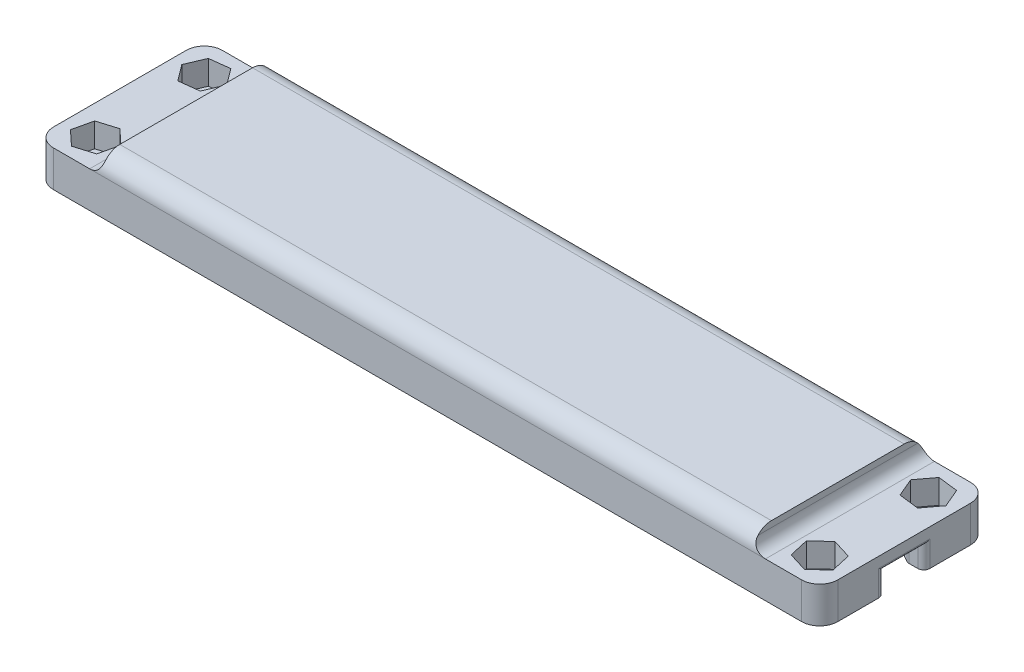
SolidWorks part; units mm, degrees
ref_plane "Front Plane" through (0, 0, 0) normal (0, 0, 1) x (1, 0, 0)
ref_plane "Top Plane" through (0, 0, 0) normal (0, 1, 0) x (1, 0, 0)
ref_plane "Right Plane" through (0, 0, 0) normal (1, 0, 0) x (0, 0, -1)
sketch "Sketch1" plane through (0, 0, 0) normal (0, 1, 0) x (1, 0, 0)
  line L1 (65, -14) -> (-65, -14)
  line L2 (65, -14) -> (65, 14)
  line L3 (65, 14) -> (-65, 14)
  line L4 (-65, -14) -> (-65, 14)
  line L5 (65, -14) -> (-65, 14) construction
  line L6 (65, 14) -> (-65, -14) construction
  point P0 (0, 0)
  dimension "D1" = 28
  dimension "D2" = 130
extrude "Boss-Extrude1" add sketch "Sketch1" along normal blind 9
sketch "Sketch2" plane through (0, 0, 0) normal (0, 1, 0) x (1, 0, 0)
  line L0 (-51, 7.5) -> (-56, 3.25)
  line L1 (27, -11.85) -> (-27, -11.85)
  line L2 (27, -11.85) -> (27, 11.85)
  line L3 (27, 11.85) -> (-27, 11.85)
  line L4 (-27, -11.85) -> (-27, 11.85)
  line L5 (27, -11.85) -> (-27, 11.85) construction
  line L6 (27, 11.85) -> (-27, -11.85) construction
  line L7 (55.3, -7.25) -> (27, -7.25)
  line L8 (55.3, -7.25) -> (55.3, 7.25)
  line L9 (55.3, 7.25) -> (27, 7.25)
  line L10 (27, -7.25) -> (27, 7.25)
  line L11 (55.3, -7.25) -> (27, 7.25) construction
  line L12 (55.3, 7.25) -> (27, -7.25) construction
  line L13 (-27, -7.5) -> (-51, -7.5)
  line L14 (-27, -7.5) -> (-27, 7.5)
  line L15 (-27, 7.5) -> (-51, 7.5)
  line L16 (-51, -7.5) -> (-51, 7.5)
  line L17 (-27, -7.5) -> (-51, 7.5) construction
  line L18 (-27, 7.5) -> (-51, -7.5) construction
  line L19 (-56, 3.25) -> (-65, 3.25)
  line L20 (-65, 14) -> (-65, -14) construction
  line L21 (-65, 3.25) -> (-65, -3.25)
  line L22 (-65, -3.25) -> (-56, -3.25)
  line L23 (-56, -3.25) -> (-51, -7.5)
  line L24 (55.3, 7.25) -> (62.3, 3.25)
  line L25 (62.3, 3.25) -> (65, 3.25)
  line L26 (65, -14) -> (65, 14) construction
  line L27 (65, 3.25) -> (65, -3.25)
  line L28 (65, -3.25) -> (62.3, -3.25)
  line L29 (62.3, -3.25) -> (55.3, -7.25)
  line L30 (-75.479, 0) -> (84.6073, 0) construction
  point P0 (0, 0)
  point P6 (41.15, 0)
  point P12 (-39, 0)
  dimension "D1" = 54
  dimension "D2" = 23.7
  dimension "D3" = 14.5
  dimension "D4" = 28.3
  dimension "D5" = 15
  dimension "D6" = 24
  dimension "D7" = 7
  dimension "D8" = 7
  dimension "D9" = 6.5
  dimension "D10" = 5
  dimension "D11" = 6.5
extrude "Cut-Extrude1" cut sketch "Sketch2" along normal blind 7 contours L4 L1 L2 L3 region at (0, 0, 0)
extrude "Cut-Extrude2" cut sketch "Sketch2<3>" along normal blind 3.75 contours L8 L9 L2 L7 | L29 L28 L27 L25 L24 L8 region at (41.15, 0, 0) region at (59.3761, 0, 0)
sketch "Sketch2<3>" plane through (0, 0, 0) normal (0, 1, 0) x (1, 0, 0) same geometry as "Sketch2"
extrude "Cut-Extrude3" cut sketch "Sketch2<4>" along normal blind 3.6 contours L16 L13 L4 L15 | L22 L23 L16 L0 L19 L21 region at (-56.9903, 0, 0) region at (-39, 0, 0)
sketch "Sketch2<4>" plane through (0, 0, 0) normal (0, 1, 0) x (1, 0, 0) same geometry as "Sketch2"
fillet "Fillet1" radius 1 20 edges at (65, 1.875, -3.25) (65, 1.875, 3.25) (-65, 1.8, -3.25) (-65, 1.8, 3.25) (-56, 1.8, 3.25) (-56, 1.8, -3.25) (-51, 1.8, -7.5) (-51, 1.8, 7.5) (-27, 1.8, -7.5) (-27, 1.8, 7.5) (55.3, 1.875, -7.25) (62.3, 1.875, -3.25) (62.3, 1.875, 3.25) (55.3, 1.875, 7.25) (27, 1.875, -7.25) (27, 1.875, 7.25) (-27, 3.5, -11.85) (-27, 3.5, 11.85) (27, 3.5, 11.85) (27, 3.5, -11.85)
fillet "Fillet2" radius 0.5 12 edges at (-26.7071, 7, 11.5571) (0, 7, 11.85) (26.7071, 7, 11.5571) (26.7071, 7, -11.5571) (0, 7, -11.85) (-26.7071, 7, -11.5571) (-65, 3.6, 0) (65, 3.75, 0) (27, 7, 0) (27, 3.75, 0) (-27, 3.6, 0) (-27, 7, 0)
fillet "Fillet3" radius 3 8 edges at (-65, 9, 0) (-65, 4.5, -14) (-65, 4.5, 14) (65, 4.5, 14) (65, 4.5, -14) (65, 9, 0) (0, 9, 14) (0, 9, -14)
sketch "Sketch3" plane through (0, 0, 0) normal (0, 1, 0) x (1, 0, 0)
  line L0 (-62, -14) -> (62, -14) construction
  line L1 (-65, -4.25) -> (-65, -11) construction
  line L2 (-65, 11) -> (-65, 4.25) construction
  line L3 (62, 14) -> (-62, 14) construction
  line L4 (65, -11) -> (65, -4.25) construction
  line L5 (65, 4.25) -> (65, 11) construction
  circle A0 centre (-60, -9) radius 1.7
  circle A1 centre (60, -9) radius 1.7
  circle A2 centre (60, 9) radius 1.7
  circle A3 centre (-60, 9) radius 1.7
  dimension "D1" = 3.4
  dimension "D2" = 5
  dimension "D10" = 3.4
  dimension "D3" = 5
  dimension "D4" = 5
  dimension "D5" = 5
  dimension "D6" = 5
  dimension "D7" = 5
  dimension "D8" = 5
  dimension "D9" = 5
extrude "Cut-Extrude4" cut sketch "Sketch3" along normal blind 13.6
ref_plane "Plane1" through (0, 9, 0) normal (0, 1, 0) x (1, 0, 0)
sketch "Sketch4" plane through (0, 9, 0) normal (0, 1, 0) x (1, 0, 0)
  line L1 (-58.6882, 12.081) -> (-62.0123, 11.6766)
  line L2 (-62.0123, 11.6766) -> (-63.3241, 8.5956)
  line L3 (-63.3241, 8.5956) -> (-61.3118, 5.919)
  line L4 (-61.3118, 5.919) -> (-57.9877, 6.3234)
  line L5 (-57.9877, 6.3234) -> (-56.6759, 9.4044)
  line L6 (-56.6759, 9.4044) -> (-58.6882, 12.081)
  line L7 (-59.2495, -5.7365) -> (-62.451, -6.7184)
  line L8 (-62.451, -6.7184) -> (-63.2015, -9.9818)
  line L9 (-63.2015, -9.9818) -> (-60.7505, -12.2635)
  line L10 (-60.7505, -12.2635) -> (-57.549, -11.2816)
  line L11 (-57.549, -11.2816) -> (-56.7985, -8.0182)
  line L12 (-56.7985, -8.0182) -> (-59.2495, -5.7365)
  line L13 (58.6882, 12.081) -> (56.6759, 9.4044)
  line L14 (56.6759, 9.4044) -> (57.9877, 6.3234)
  line L15 (57.9877, 6.3234) -> (61.3118, 5.919)
  line L16 (61.3118, 5.919) -> (63.3241, 8.5956)
  line L17 (63.3241, 8.5956) -> (62.0123, 11.6766)
  line L18 (62.0123, 11.6766) -> (58.6882, 12.081)
  line L19 (59.2495, -5.7365) -> (56.7985, -8.0182)
  line L20 (56.7985, -8.0182) -> (57.549, -11.2816)
  line L21 (57.549, -11.2816) -> (60.7505, -12.2635)
  line L22 (60.7505, -12.2635) -> (63.2015, -9.9818)
  line L23 (63.2015, -9.9818) -> (62.451, -6.7184)
  line L24 (62.451, -6.7184) -> (59.2495, -5.7365)
  circle A0 centre (-60, 9) radius 2.9 construction
  circle A1 centre (-60, -9) radius 2.9 construction
  circle A2 centre (60, 9) radius 2.9 construction
  circle A3 centre (60, -9) radius 2.9 construction
  circle A4 centre (-60, 9) radius 1.7 construction
  circle A5 centre (-60, -9) radius 1.7 construction
  circle A6 centre (60, -9) radius 1.7 construction
  circle A7 centre (60, 9) radius 1.7 construction
  dimension "D2" = 5.8
  dimension "D1" = 5.8
  dimension "D3" = 5.8
  dimension "D4" = 5.8
  dimension "D5" = 5.8
  dimension "D6" = 3.3486
extrude "Cut-Extrude5" cut sketch "Sketch4" against normal blind 7
sketch "Sketch5" plane through (0, 9, 0) normal (0, 1, 0) x (1, 0, 0)
  line L0 (0, 33.509) -> (0, -33.509) construction
  line L2 (-54, 3) -> (-54, 15)
  line L3 (-54, 15) -> (-66, 15)
  line L4 (-66, 3) -> (-66, 15)
  line L5 (-54, 3) -> (-66, 15) construction
  line L6 (-54, 15) -> (-66, 3) construction
  line L7 (-66, -3) -> (-66, 3)
  line L8 (-54, -3) -> (-54, 3)
  line L9 (-68.7642, 0) -> (69.3125, 0) construction
  line L11 (-54, -15) -> (-66, -3) construction
  line L12 (-54, -3) -> (-66, -15) construction
  line L13 (-66, -3) -> (-66, -15)
  line L14 (-54, -15) -> (-66, -15)
  line L15 (-54, -3) -> (-54, -15)
  line L16 (54, -3) -> (66, -15) construction
  line L17 (54, -15) -> (66, -3) construction
  line L18 (54, -3) -> (54, -15)
  line L19 (54, -15) -> (66, -15)
  line L20 (66, -3) -> (66, -15)
  line L23 (54, 15) -> (66, 3) construction
  line L24 (54, 3) -> (66, 15) construction
  line L25 (66, 3) -> (66, 15)
  line L26 (54, 15) -> (66, 15)
  line L27 (54, 3) -> (54, 15)
  line L28 (54, -3) -> (54, 3)
  line L29 (66, -3) -> (66, 3)
  point P0 (-60, 9)
  point P16 (-60, -9)
  point P21 (60, -9)
  point P26 (60, 9)
  dimension "D1" = 12
  dimension "D2" = 12
extrude "Cut-Extrude6" cut sketch "Sketch5" against normal blind 3
fillet "Fillet4" radius 2 2 edges at (54, 6, 0) (-54, 6, 0)
